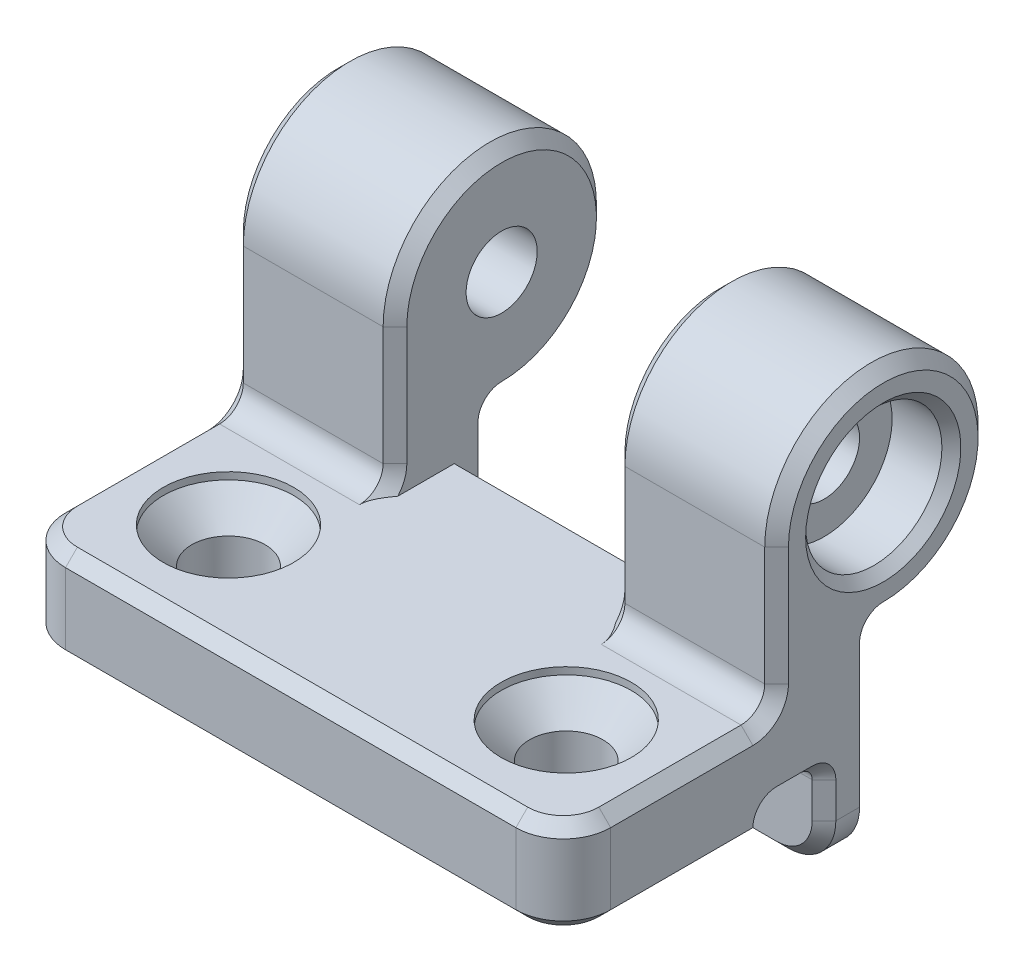
SolidWorks part; units mm, degrees
note: The reader was unsure of these and kept them because the rebuilt part matched: shared geometry of "Sketch11<3>".
material "POM Acetal Copolymer"
ref_plane "Front" through (0, 0, 0) normal (0, 0, 1) x (1, 0, 0)
ref_plane "Top" through (0, 0, 0) normal (0, 1, 0) x (1, 0, 0)
ref_plane "Right" through (0, 0, 0) normal (1, 0, 0) x (0, 0, -1)
ref_plane "Plane1" through (145.3401, 0, 0) normal (1, 0, 0) x (0, 0, -1)
sketch "Sketch5" plane through (0, 0, 0) normal (1, 0, 0) x (0, 0, -1)
  line L0 (-5, -10) -> (-5, -9)
  line L1 (-0.5, -13) -> (-2.5, -13)
  line L2 (-2.5, -13) -> (-2.5, -9)
  line L3 (-5, -10) -> (-13.5, -10)
  line L4 (-13.5, -10) -> (-13.5, -6)
  line L5 (-13.5, -6) -> (-5.5, -6)
  line L6 (-5, -9) -> (-2.5, -9)
  line L7 (-4.5, 0) -> (-4.5, -5)
  line L9 (-0.5, -5) -> (-0.5, -13)
  arc A1 (-5.5, -6) -> (-4.5, -5) centre (-5.5, -5) ccw
  arc A2 (-4.5, 0) -> (0, -4.5) centre (0, 0) cw
  circle A3 centre (0, 0) radius 1.5
  arc A4 (-0.5, -5) -> (0, -4.5) centre (0, -5) cw
  dimension "D4" = 2.5
  dimension "D7" = 4.5
  dimension "D9" = 3
  dimension "D12" = 1
  dimension "D10" = 0.5
  dimension "D2" = 2
  dimension "D3" = 10
  dimension "D5" = 4
  dimension "D6" = 11
  dimension "D8" = 2
  dimension "D11" = 13
  dimension "D13" = 1
extrude "Boss-Extrude2" add sketch "Sketch5" along normal mid plane 23 separate body
sketch "Sketch7" plane through (0, -6, -11) normal (0, -1, 0) x (-1, 0, 0)
  line L0 (-4.6, -17.5) -> (-4.6, -6.5)
  line L1 (-4.6, -6.5) -> (4.6, -6.5)
  line L2 (4.6, -6.5) -> (4.6, -17.5)
  line L3 (4.6, -17.5) -> (-4.6, -17.5)
  line L4 (0, -32) -> (0, -6.5) construction
  line L6 (11.5, -6.5) -> (-11.5, -6.5) construction
  dimension "D1" = 9.2
  dimension "D2" = 11
extrude "Cut-Extrude2" cut sketch "Sketch7" against normal through all
fillet "Fillet2" radius 2 4 edges at (11.5, -13, 1.5) (-11.5, -13, 1.5) (-11.5, -8, 13.5) (11.5, -8, 13.5)
sketch "Sketch16" plane through (-4.6, 0, 0) normal (1, 0, 0) x (0, 0, -1)
  line L0 (-2, -6) -> (-0.5, -6)
  line L1 (-5.5, -6) -> (-0.5, -6) construction
  line L2 (-0.5, -6) -> (-0.5, -7.5)
  line L3 (-0.5, -7.5) -> (-2, -6)
  dimension "D1" = 1.5
extrude "Cut-Extrude9" cut sketch "Sketch16" along normal up to vertex (9.2 mm away) up to point (4.6, -6, 0.5)
fillet "Fillet3" radius 0.5 3 edges at (0, -10, 5) (0, -9, 5) (0, -9, 2.5)
chamfer "Chamfer2" distance 0.5 angle 45 46 edges at (4.6, -5.7071, 4.7929) (-4.6, -5.7071, 4.7929) (4.6, 3.182, -3.182) (-4.6, 3.182, -3.182) (-11.5, -10, 8.5) (-10.9142, -10, 12.9142) (0, -10, 13.5) (-11.5, -10.25, 2.5) (10.9142, -10, 12.9142) (-10.9142, -12.4142, 2.5) (11.5, -10, 8.5) (0, -13, 2.5) (10.9142, -12.4142, 2.5) (11.5, -10.25, 2.5) (-11.5, 3.182, -3.182) (-11.5, -2.5, 4.5) (-11.5, -4.6464, 0.3536) (-11.5, -5.7071, 4.7929) (-11.5, -8, 0.5) (-11.5, -6, 8.5) (-10.9142, -12.4142, 0.5) (-10.9142, -6, 12.9142) (0, -13, 0.5) (0, -6, 13.5) (10.9142, -12.4142, 0.5) (10.9142, -6, 12.9142) (11.5, -8, 0.5) (11.5, -6, 8.5) (11.5, -4.6464, 0.3536) (11.5, -5.7071, 4.7929) (11.5, -2.5, 4.5) (11.5, 3.182, -3.182) (-4.6, -6.25, 0.5) (-4.6, -4.6464, 0.3536) (-4.6, -2.5, 4.5) (4.6, -6.25, 0.5) (4.6, -4.6464, 0.3536) (4.6, -2.5, 4.5) (-11.5, -9.8536, 5.1464) (11.5, -9.8536, 5.1464) (-11.5, -9.1464, 4.8536) (11.5, -9.1464, 4.8536) (-11.5, -9, 3.75) (11.5, -9, 3.75) (-11.5, -9.1464, 2.6464) (11.5, -9.1464, 2.6464)
ref_plane "Plane3" through (8.05, 0, 0) normal (-1, 0, 0) x (0, 0, 1)
sketch "Sketch11" plane through (-11.5, 0, 0) normal (-1, 0, 0) x (0, 0, 1)
  line L0 (-0.5031, 3.1353) -> (0.5031, 3.1353)
  line L1 (2.4637, 2.0034) -> (2.9668, 1.1319)
  line L2 (2.9668, -1.1319) -> (2.4637, -2.0034)
  line L3 (0.5031, -3.1353) -> (-0.5031, -3.1353)
  line L4 (-2.4637, -2.0034) -> (-2.9668, -1.1319)
  line L5 (-2.9668, 1.1319) -> (-2.4637, 2.0034)
  line L6 (-1.5877, 2.75) -> (1.5877, 2.75)
  line L7 (1.5877, 2.75) -> (3.1754, 0)
  line L8 (3.1754, 0) -> (1.5877, -2.75)
  line L9 (1.5877, -2.75) -> (-1.5877, -2.75)
  line L10 (-1.5877, -2.75) -> (-3.1754, 0)
  line L11 (-3.1754, 0) -> (-1.5877, 2.75)
  arc A0 (0.5031, 3.1353) -> (2.4637, 2.0034) centre (0.5031, 0.8714) cw
  arc A1 (2.9668, 1.1319) -> (2.9668, -1.1319) centre (1.0062, 0) cw
  arc A2 (2.4637, -2.0034) -> (0.5031, -3.1353) centre (0.5031, -0.8714) cw
  arc A3 (-0.5031, -3.1353) -> (-2.4637, -2.0034) centre (-0.5031, -0.8714) cw
  arc A4 (-2.9668, -1.1319) -> (-2.9668, 1.1319) centre (-1.0062, 0) cw
  arc A5 (-2.4637, 2.0034) -> (-0.5031, 3.1353) centre (-0.5031, 0.8714) cw
  circle A6 centre (0, 0) radius 1.5 construction
  circle A7 centre (0, 0) radius 2.875 construction
  circle A8 centre (0, 0) radius 3.1754 construction
  circle M15 centre (0, 0) radius 1.5
  dimension "D1" = 5.75
  dimension "D2" = 5.5
  dimension "D3" = 0.3853
extrude "Cut-Extrude4" cut sketch "Sketch11" against normal blind 3.5 contours L11 L10 L9 L8 L7 L6 M15
extrude "Cut-Extrude5" cut sketch "Sketch11<3>" against normal blind 1 draft 45 contours L0 A0 L1 A1 L2 A2 L3 A3 L4 A4 L5 A5
sketch "Sketch11<3>" plane through (-11.5, 0, 0) normal (-1, 0, 0) x (0, 0, 1) same geometry as "Sketch11"
sketch "Sketch12" plane through (11.5, 0, 0) normal (1, 0, 0) x (0, 0, -1)
  circle A0 centre (0, 0) radius 2.875 construction
  circle A1 centre (0, 0) radius 2.875
extrude "Cut-Extrude6" cut sketch "Sketch12" against normal blind 2.5
chamfer "Chamfer3" distance 0.4 angle 45 1 edges at (11.5, 0, -2.875)
sketch "Sketch14" plane through (0, -6, 0) normal (0, 1, 0) x (1, 0, 0)
  line L0 (7.125, -4.5) -> (7.125, -9) construction
  line L2 (7.125, -9) -> (11.5, -9) construction
  line L3 (11.5, -5.5) -> (11.5, -11.5) construction
  line L4 (7.125, -9) -> (7.125, -13.5) construction
  line L5 (9.5, -13.5) -> (-9.5, -13.5) construction
  line L6 (0, -13.5) -> (0, -5.2206) construction
  circle A0 centre (7.125, -9) radius 2.75
  circle A1 centre (-7.125, -9) radius 2.75
  dimension "D1" = 5.5
  dimension "D2" = 14.25
extrude "Cut-Extrude7" cut sketch "Sketch14" against normal blind 0.3
sketch "Sketch15" plane through (0, -6.3, 0) normal (0, 1, 0) x (1, 0, 0)
  circle A0 centre (7.125, -9) radius 1.55
  circle A1 centre (-7.125, -9) radius 1.55
  dimension "D1" = 3.1
extrude "Cut-Extrude8" cut sketch "Sketch15" against normal up to next
chamfer "Chamfer4" distance 1.2 angle 45 2 edges at (-7.125, -6.3, 10.55) (7.125, -6.3, 10.55)
move or copy body "Body-Move/Copy1" [suppressed] bodies to move or copy 117 placed by mates yes
